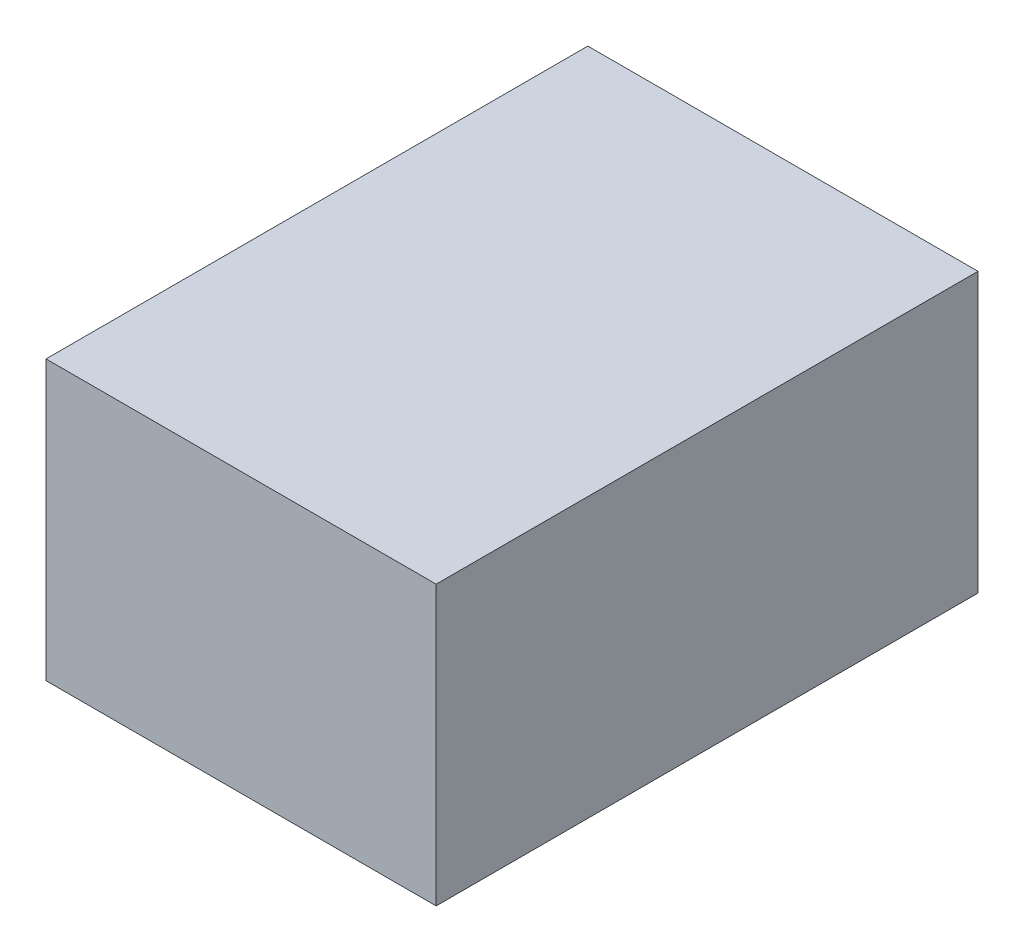
SolidWorks part; units mm, degrees
ref_plane "Front Plane" through (0, 0, 0) normal (0, 0, 1) x (1, 0, 0)
ref_plane "Top Plane" through (0, 0, 0) normal (0, 1, 0) x (1, 0, 0)
ref_plane "Right Plane" through (0, 0, 0) normal (1, 0, 0) x (0, 0, -1)
sketch "Sketch1" plane through (0, 0, 0) normal (0, 1, 0) x (1, 0, 0)
  line L1 (-32.004, -44.45) -> (32.004, -44.45)
  line L2 (-32.004, -44.45) -> (-32.004, 44.45)
  line L3 (-32.004, 44.45) -> (32.004, 44.45)
  line L4 (32.004, -44.45) -> (32.004, 44.45)
  line L5 (-32.004, -44.45) -> (32.004, 44.45) construction
  line L6 (-32.004, 44.45) -> (32.004, -44.45) construction
  point P0 (0, 0)
  dimension "D1" = 88.9
  dimension "D2" = 64.008
extrude "Boss-Extrude1" add sketch "Sketch1" along normal blind 22.86 and the other way blind 22.86
